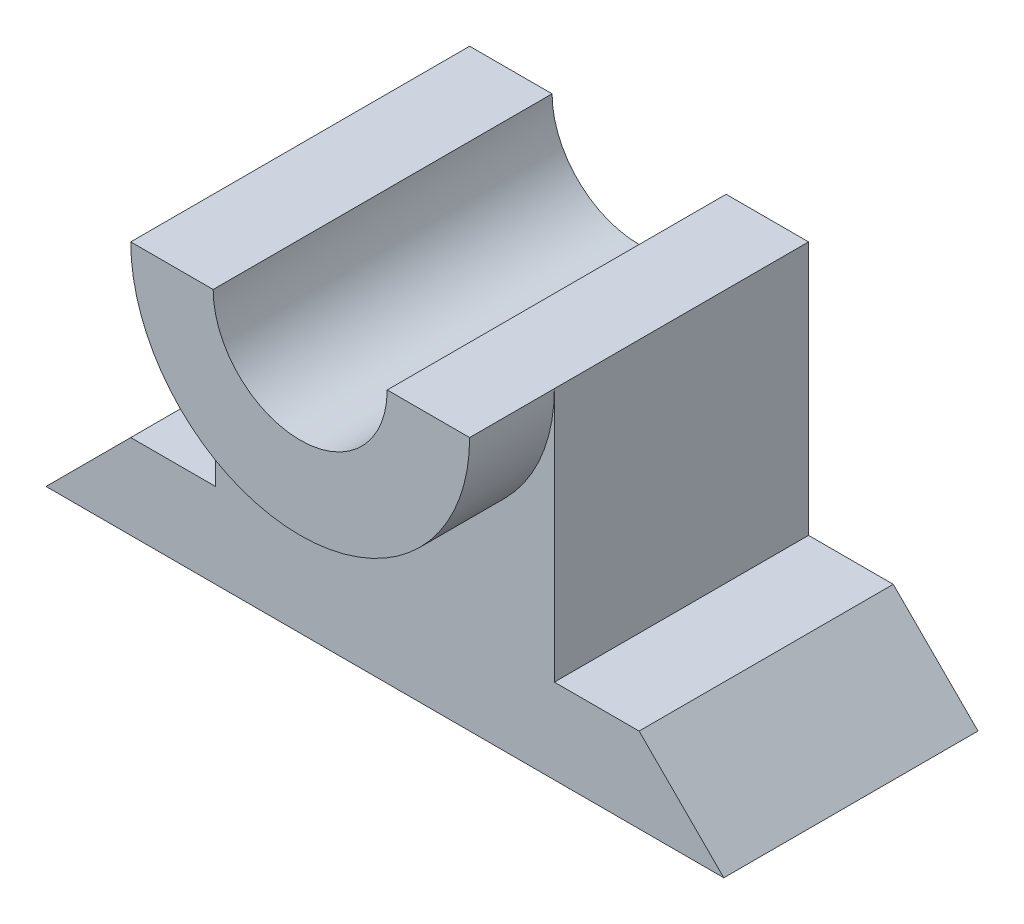
SolidWorks part; units mm, degrees
ref_plane "Front Plane" through (0, 0, 0) normal (0, 0, 1) x (1, 0, 0)
ref_plane "Top Plane" through (0, 0, 0) normal (0, 1, 0) x (1, 0, 0)
ref_plane "Right Plane" through (0, 0, 0) normal (1, 0, 0) x (0, 0, -1)
sketch "Sketch1" plane through (0, 0, 0) normal (0, 0, 1) x (1, 0, 0)
  line L0 (0, 0) -> (0, -1016) construction
  line L1 (508, 0) -> (508, -762)
  line L2 (-508, 0) -> (-508, -762)
  line L3 (508, -762) -> (762, -762)
  line L4 (-508, -762) -> (-762, -762)
  line L5 (762, -762) -> (1016, -1016)
  line L6 (-762, -762) -> (-1016, -1016)
  line L7 (1016, -1016) -> (-1016, -1016)
  line L8 (-508, 0) -> (-260.8532, 0)
  line L9 (260.8532, 0) -> (508, 0)
  arc A0 (-260.8532, 0) -> (260.8532, 0) centre (0, 0) ccw
  arc A1 (-508, 0) -> (508, 0) centre (0, 0) ccw
  point P3 (384.4266, 0)
  dimension "D1" = 1016
  dimension "D2" = 2032
  dimension "D4" = 260.8532
  dimension "D5" = 508
  dimension "D3" = 254
extrude "Boss-Extrude1" add sketch "Sketch1" along normal blind 762 contours A1 L0 L7 L5 L3 L1 | L0 A1 L2 L4 L6 L7 region at (379.4975, -745.6794, 0) region at (-379.4975, -745.6794, 0)
extrude "Boss-Extrude2" add sketch "Sketch1<3>" along normal blind 1016 contours L0 A0 L8 A1 | A0 L0 A1 L9 region at (253.1629, -253.1629, 0) region at (-253.1629, -253.1629, 0)
sketch "Sketch1<3>" plane through (0, 0, 0) normal (0, 0, 1) x (1, 0, 0) same geometry as "Sketch1"
